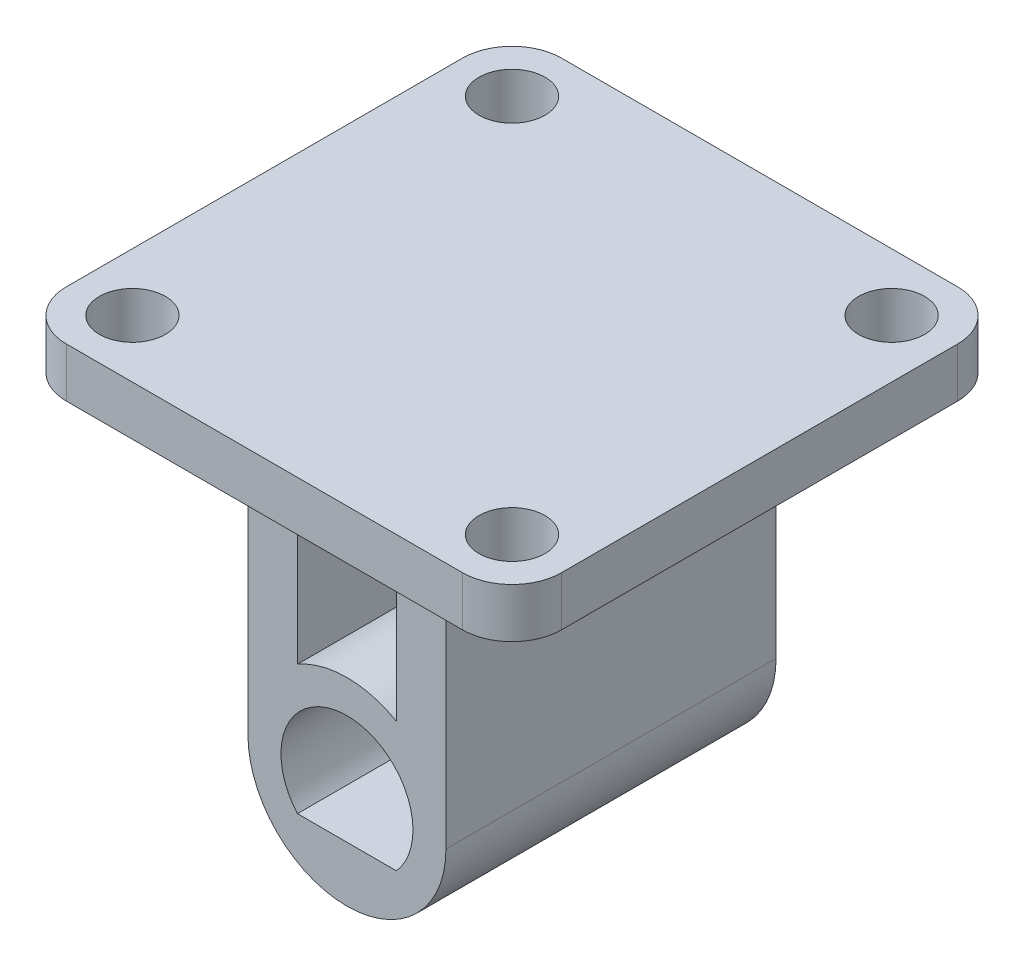
SolidWorks part; units mm, degrees
ref_plane "Alzado" through (0, 0, 0) normal (0, 0, 1) x (1, 0, 0)
ref_plane "Planta" through (0, 0, 0) normal (0, 1, 0) x (1, 0, 0)
ref_plane "Vista lateral" through (0, 0, 0) normal (1, 0, 0) x (0, 0, -1)
sketch "Croquis1" plane through (0, 0, 0) normal (0, 1, 0) x (1, 0, 0)
  line L0 (0, 0) -> (8.5714, 0) construction
  line L1 (0, 0) -> (0, -8.3442) construction
  line L2 (-15, 15) -> (15, 15)
  line L3 (15, 15) -> (15, -15)
  line L4 (15, -15) -> (-15, -15)
  line L5 (-15, -15) -> (-15, 15)
  dimension "D1" = 30
  dimension "D2" = 30
extrude "Saliente-Extruir1" add sketch "Croquis1" along normal blind 3
ref_plane "Plano1" through (0, 0, 10) normal (0, 0, 1) x (1, 0, 0)
sketch "Croquis3" plane through (0, 0, 10) normal (0, 0, 1) x (1, 0, 0)
  line L0 (0, 0) -> (0, 4.8812) construction
  line L5 (0, 0) -> (0, -9.5797) construction
  line L6 (-3, 0) -> (-3, -11.8038)
  line L11 (-6, 0) -> (-6, -17)
  line L12 (-15, 0) -> (15, 0) construction
  line L13 (6, -17) -> (6, 0)
  line L14 (6, 0) -> (3, 0)
  line L17 (-3, 0) -> (-6, 0)
  line L19 (3, -11.8038) -> (3, 0)
  line L20 (-3, -19.6458) -> (3, -19.6458)
  arc A2 (-6, -17) -> (6, -17) centre (0, -17) ccw
  arc A8 (-3, -11.8038) -> (3, -11.8038) centre (0, -17) cw
  arc A9 (3, -19.6458) -> (-3, -19.6458) centre (0, -17) ccw
  dimension "D1" = 6
  dimension "D3" = 17
  dimension "D5" = 6
  dimension "D4" = 6
  dimension "D8" = 3
  dimension "D6" = 6
  dimension "D2" = 4
  dimension "D7" = 6
extrude "Saliente-Extruir2" add sketch "Croquis3" against normal blind 20
sketch "Croquis4" plane through (0, 3, 0) normal (0, 1, 0) x (1, 0, 0)
  line L0 (0, 0) -> (-3.4922, 0) construction
  line L1 (0, 0) -> (0, 4.1707) construction
  circle A0 centre (-11.5, 11.5) radius 2
  circle A1 centre (11.5, 11.5) radius 2
  circle A2 centre (11.5, -11.5) radius 2
  circle A3 centre (-11.5, -11.5) radius 2
  dimension "D1" = 4
  dimension "D2" = 4
  dimension "D3" = 4
  dimension "D4" = 4
  dimension "D5" = 23
  dimension "D6" = 23
extrude "Cortar-Extruir1" cut sketch "Croquis4" against normal through all
fillet "Redondeo2" radius 3 4 edges at (15, 1.5, -15) (-15, 1.5, -15) (15, 1.5, 15) (-15, 1.5, 15)
fillet "Redondeo4" radius 2 2 edges at (-3, 0, 0) (3, 0, 0)
fillet "Redondeo5" radius 3 6 edges at (3.5, 0, -10) (-3.5, 0, -10) (-3.5, 0, 10) (3.5, 0, 10) (6, 0, 0) (-6, 0, 0)
